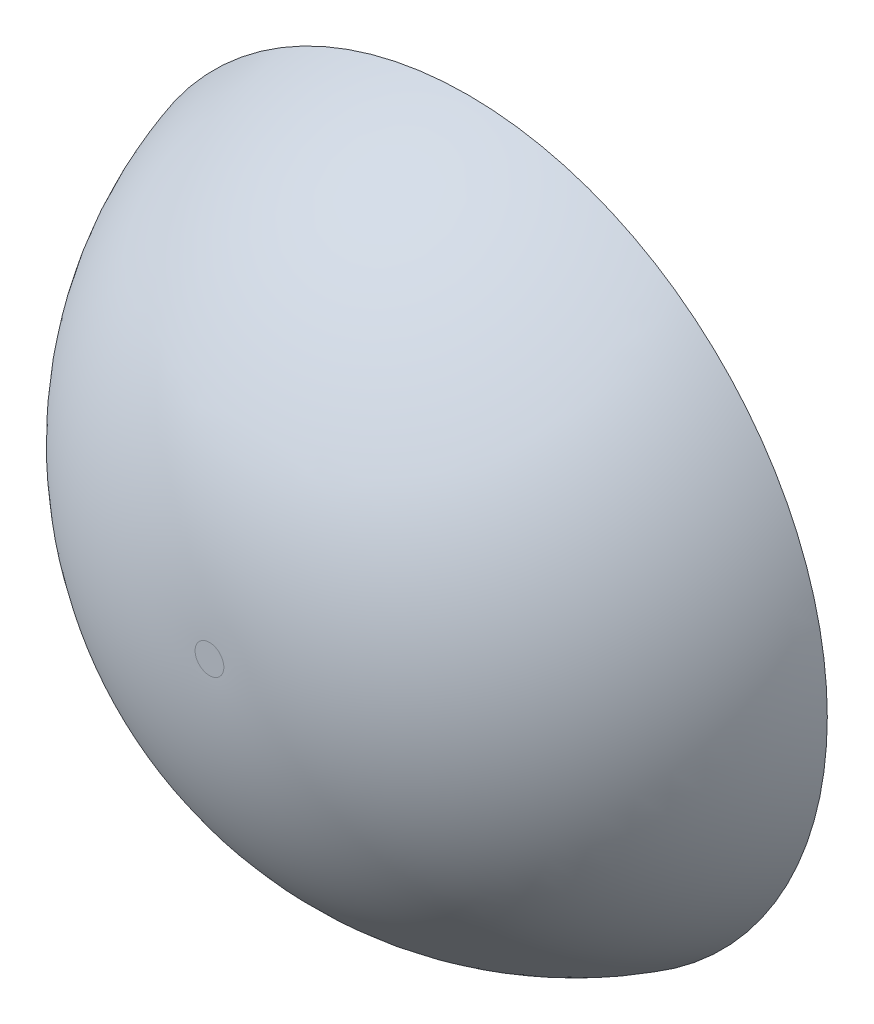
SolidWorks part; units mm, degrees
ref_plane "Plan de face" through (0, 0, 0) normal (0, 0, 1) x (1, 0, 0)
ref_plane "Plan de dessus" through (0, 0, 0) normal (0, 1, 0) x (1, 0, 0)
ref_plane "Plan de droite" through (0, 0, 0) normal (1, 0, 0) x (0, 0, -1)
sketch "Esquisse1" plane through (0, 0, 0) normal (0, 0, 1) x (1, 0, 0)
  circle A0 centre (0, 0) radius 25
  dimension "D1" = 50
extrude "Boss.-Extru.1" add sketch "Esquisse1" along normal blind 18
fillet "Congé1" radius 25 1 edges at (25, 0, 18)
sketch "Esquisse3" plane through (0, 0, 0) normal (0, 1, 0) x (1, 0, 0)
  line L0 (0, -13) -> (30.8305, 15.7499) construction
  line L1 (16.8211, 2.686) -> (3.6568, -9.59)
  line L2 (16.8211, 2.686) -> (18.2874, 1.1136)
  line L3 (3.6568, -9.59) -> (5.1231, -11.1624)
  line L4 (18.2874, 1.1136) -> (5.1231, -11.1624)
  line L5 (25, 0) -> (-25, 0) construction
  dimension "D1" = 4.3
  dimension "D2" = 13
  dimension "D3" = 43
  dimension "D4" = 5
  dimension "D5" = 18
revolve "Enlèvement de matière-Révolution1" cut sketch "Esquisse3" angle 360 about L0
pattern_circular "Répétition circulaire1" count 3 over 360 about axis through (0, 0, 0) along (0, 0, 1) of "Enlèvement de matière-Révolution1"
